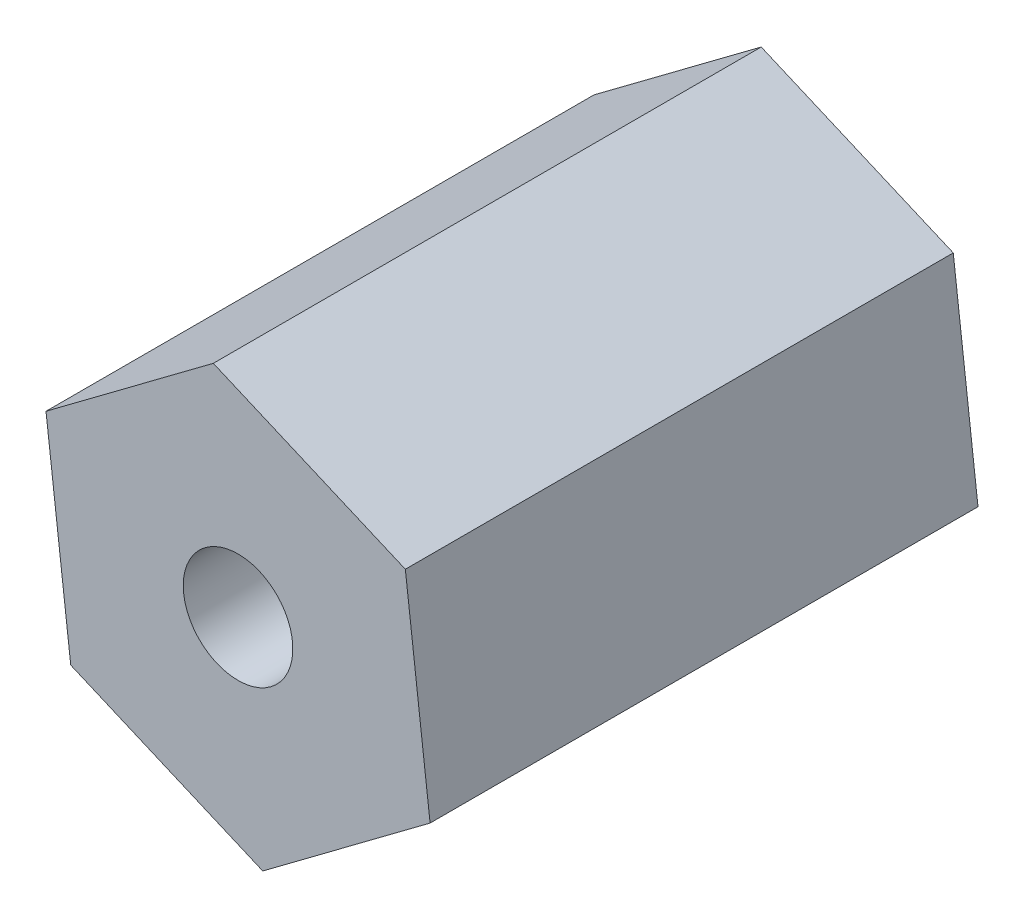
SolidWorks part; units mm, degrees
ref_plane "Front Plane" through (0, 0, 0) normal (0, 0, 1) x (1, 0, 0)
ref_plane "Top Plane" through (0, 0, 0) normal (0, 1, 0) x (1, 0, 0)
ref_plane "Right Plane" through (0, 0, 0) normal (1, 0, 0) x (0, 0, -1)
sketch "Sketch7" plane through (0, 0, 0) normal (0, 0, 1) x (1, 0, 0)
  line L1 (-76.3814, 4.7135) -> (-76.8116, 8.3202)
  line L2 (-76.8116, 8.3202) -> (-80.1501, 9.751)
  line L3 (-80.1501, 9.751) -> (-83.0584, 7.5751)
  line L4 (-83.0584, 7.5751) -> (-82.6283, 3.9685)
  line L5 (-82.6283, 3.9685) -> (-79.2898, 2.5377)
  line L6 (-79.2898, 2.5377) -> (-76.3814, 4.7135)
  circle A0 centre (-79.7199, 6.1443) radius 3.1456 construction
  circle A1 centre (-79.7199, 6.1443) radius 0.9525
  dimension "D2" = 1.905
  dimension "D1" = 7.2644
extrude "Boss-Extrude4" add sketch "Sketch7" along normal blind 9.525 separate body
ref_axis "Axis2" through (-79.7199, 6.1443, 16.4297) along (0, 0, -1)
